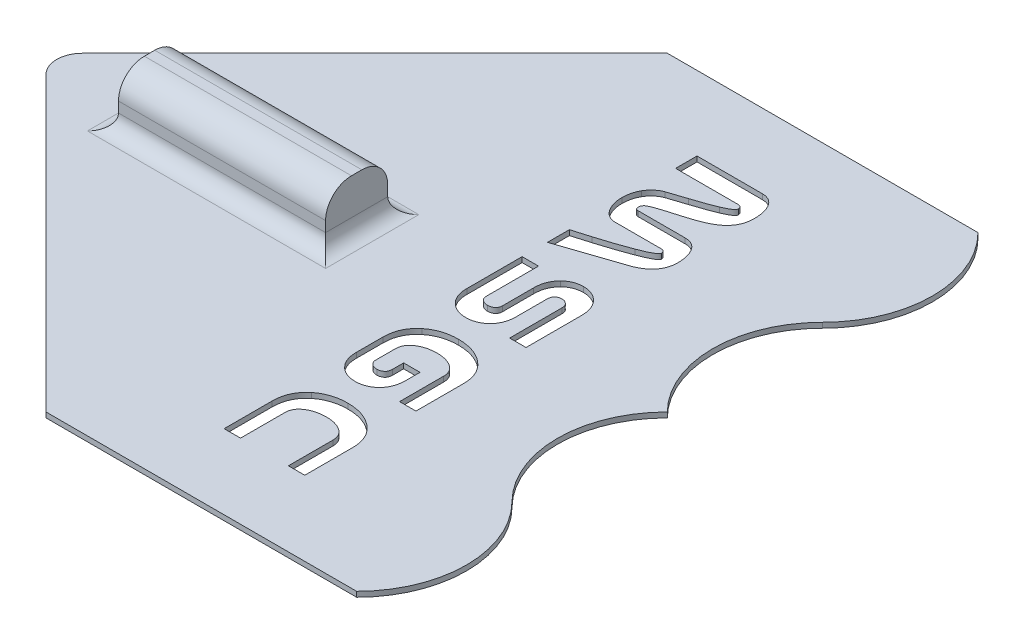
SolidWorks part; units mm, degrees
ref_plane "Front Plane" through (0, 0, 0) normal (0, 0, 1) x (1, 0, 0)
ref_plane "Top Plane" through (0, 0, 0) normal (0, 1, 0) x (1, 0, 0)
ref_plane "Right Plane" through (0, 0, 0) normal (1, 0, 0) x (0, 0, -1)
sketch "Sketch1" plane through (0, 0, 0) normal (0, 1, 0) x (1, 0, 0)
  line L0 (0, 0) -> (60, 0)
  line L1 (0, 0) -> (60, 60)
  line L2 (60, 60) -> (120, 60)
  line L3 (120, 60) -> (120, -60)
  line L4 (60, -60) -> (120, -60)
  line L5 (0, 0) -> (60, -60)
  line L6 (120, -30) -> (120, 30)
  arc A0 (120, 60) -> (120, 30) centre (105, 45) cw
  arc A1 (120, 30) -> (120, 0) centre (135, 15) ccw
  arc A2 (120, 0) -> (120, -30) centre (135, -15) ccw
  arc A3 (120, -30) -> (120, -60) centre (105, -45) cw
  point P8 (120, 0)
  dimension "D1" = 60
  dimension "D2" = 60
  dimension "D3" = 60
  dimension "D4" = 120
  dimension "D5" = 60
extrude "Boss-Extrude1" add sketch "Sketch1" along normal blind 1 contours A2 A1 L3 L2 L1 L5 L4 | A3 L3 | A0 L3 region at (72.2578, 0, 0) region at (122.5194, 0, -45) region at (122.5194, 0, 45)
sketch "Sketch2" plane through (0, 1, 0) normal (0, 1, 0) x (1, 0, 0)
  line L0 (0, 0) -> (40, 0)
  line L2 (20, -6) -> (60, -6)
  line L3 (20, -6) -> (20, 6)
  line L4 (20, 6) -> (60, 6)
  line L5 (60, -6) -> (60, 6)
  line L6 (20, -6) -> (60, 6) construction
  line L7 (20, 6) -> (60, -6) construction
  dimension "D1" = 40
  dimension "D2" = 40
  dimension "D3" = 12
extrude "Boss-Extrude2" add sketch "Sketch2" along normal blind 10 contours L2 L5 L4 L3 region at (20.4176, 1, 3)
sketch "Sketch3" plane through (20, 0, 0) normal (-1, 0, 0) x (0, 0, 1)
  line L0 (0, 0) -> (0, 5)
  line L2 (0, 1.1109) -> (3.8891, 5)
  line L3 (0, 1.1109) -> (-3.8891, 5)
  line L4 (-3.8891, 5) -> (0, 8.8891)
  line L5 (3.8891, 5) -> (0, 8.8891)
  line L6 (0, 1.1109) -> (0, 8.8891) construction
  line L7 (-3.8891, 5) -> (3.8891, 5) construction
  dimension "D1" = 5
  dimension "D2" = 5.5
  dimension "D3" = 5.5
extrude "Cut-Extrude1" cut sketch "Sketch3" against normal blind 35 contours L2 L5 L4 L3 region at (20, 3.1332, -1.8668)
fillet "Fillet1" radius 5 2 edges at (40, 11, 6) (40, 11, -6)
fillet "Fillet2" radius 3 4 edges at (60, 1, 0) (40, 1, -6) (40, 1, 6) (20, 1, 0)
sketch "Sketch4" plane through (0, 1, 0) normal (0, 1, 0) x (1, 0, 0)
  line L0 (0, 0) -> (80, 0) construction
  line L1 (80, 60) -> (80, -60) construction
  line L2 (60, -60) -> (120, -60) construction
  text T0 "MSGC" font "Nasa" height in points 60
  point P8 (80, 0)
  dimension "D1" = 80
extrude "Cut-Extrude3" cut sketch "Sketch4" against normal blind 10.5
fillet "Fillet3" radius 5 1 edges at (0, 0.5, 0)
